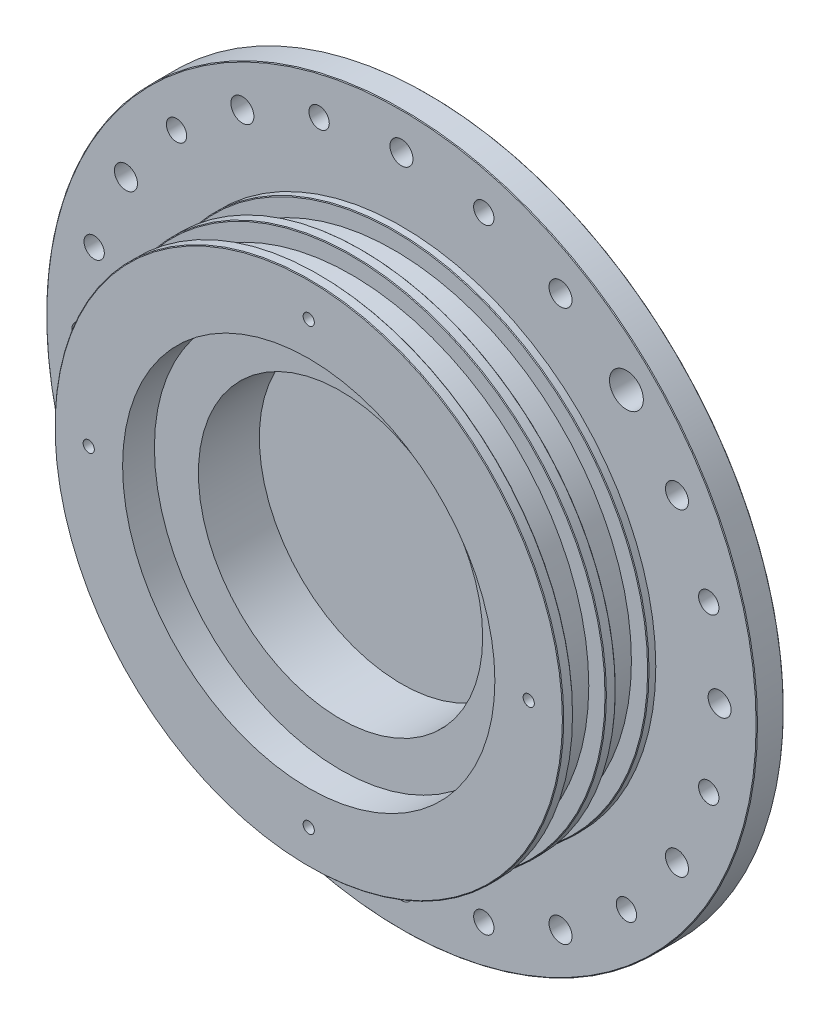
SolidWorks part; units mm, degrees
other "Marquage1"
sketch "Esquisse22" plane through (-100, 100, -114.225) normal (-0.6969, 0.6451, 0.3132) x (0.5706, 0.7634, -0.3027)
sketch "Esquisse26" plane through (-110, 110, -114.225) normal (-0.6969, 0.6451, 0.3132) x (0.5706, 0.7634, -0.3027)
sketch "Esquisse28" plane through (-110, 110, -114.225) normal (-0.6969, 0.6451, 0.3132) x (0.5706, 0.7634, -0.3027)
sketch "Esquisse31" plane through (-110, 110, -114.225) normal (-0.6969, 0.6451, 0.3132) x (0.5706, 0.7634, -0.3027)
sketch "Esquisse32" plane through (-100, 100, -114.225) normal (-0.6969, 0.6451, 0.3132) x (0.5706, 0.7634, -0.3027)
material "AISI 316 Barre d'acier inoxydable recuit (SS)"
ref_plane "Plan de face" through (0, 0, 0) normal (0, 0, 1) x (1, 0, 0)
ref_plane "Plan de dessus" through (0, 0, 0) normal (0, 1, 0) x (1, 0, 0)
ref_plane "Plan de droite" through (0, 0, 0) normal (1, 0, 0) x (0, 0, -1)
sketch "Esquisse1" plane through (0, 0, 0) normal (0, 1, 0) x (1, 0, 0)
  line L0 (87.5, 35.4) -> (0, 35.4)
  line L1 (0, 35.4) -> (0, 0)
  line L2 (0, 0) -> (75.15, 0)
  line L3 (75.15, 0) -> (75.15, 3)
  line L4 (75.15, 3) -> (70.15, 3)
  line L5 (70.15, 3) -> (70.15, 12.6)
  line L6 (70.15, 12.6) -> (75.15, 12.6)
  line L7 (75.15, 12.6) -> (75.15, 15.6)
  line L8 (75.15, 15.6) -> (70.15, 15.6)
  line L9 (70.15, 15.6) -> (70.15, 25.2)
  line L10 (70.15, 25.2) -> (75.15, 25.2)
  line L11 (75.15, 25.2) -> (75.15, 27.4)
  line L12 (75.15, 27.4) -> (87.5, 27.4)
  line L13 (87.5, 27.4) -> (87.5, 35.4)
  line L14 (0, 35.4) -> (0, 0) construction
  dimension "D1" = 8
  dimension "D2" = 2.2
  dimension "D3" = 9.6
  dimension "D4" = 3
  dimension "D5" = 9.6
  dimension "D6" = 3
  dimension "D7" = 5
  dimension "D8" = 75.15
  dimension "D9" = 87.5
revolve "Révolution1" add sketch "Esquisse1" angle 360 about L14 reverse direction yes
hole_wizard "Diamètre du perçage Ø9.0 (9)1" positions "Esquisse3" profile "Esquisse2" hole size "Ø9.0" standard "Ansi Metric"
sketch "Esquisse3" plane through (0, 0, -27.4) normal (0, 0, 1) x (1, 0, 0)
  point P0 (-87.5, 0)
  point P1 (0, 87.5)
  point P2 (0, -87.5)
  point P3 (87.5, 0)
sketch "Esquisse2" plane through (-87.5, 0, -27.4) normal (1, 0, 0) x (0, -1, 0)
  line L0 (0, 0) -> (0, 3)
  line L1 (0, 3) -> (4.5, 3)
  line L2 (4.5, 3) -> (4.5, 0)
  line L5 (4.5, 0) -> (0, 0)
  line L10 (0, 3) -> (-4.5, 3) construction
  line L11 (0, -6.35) -> (0, 107.95) construction
  dimension "Diamètre du perçage" = 9
  dimension "Profondeur du perçage" = 3
  dimension "Angle de pointe" = 180
hole_wizard "Trou taraudé M4x0.71" positions "Esquisse44" profile "Esquisse45" tap size "M4x0.7" standard "Ansi Metric"
sketch "Esquisse44" plane through (0, 0, 0) normal (0, 0, 1) x (1, 0, 0)
  point P0 (0, 65)
  dimension "D1" = 65
sketch "Esquisse45" plane through (0, 65, 0) normal (1, 0, 0) x (0, -1, 0)
  line L0 (0, 0) -> (0, 15)
  line L1 (0, 15) -> (1.65, 15)
  line L2 (1.65, 15) -> (1.65, 0)
  line L5 (1.65, 0) -> (0, 0)
  line L10 (0, 15) -> (-1.65, 15) construction
  line L11 (0, -6.35) -> (0, 107.95) construction
  dimension "Diamètre du trou pour taraudage" = 3.3
  dimension "Profondeur du trou pour taraudage" = 15
  dimension "Angle de pointe" = 180
cosmetic thread "Filetage de perçage3" parameters "D1"=15, "D2"=4
pattern_circular "Répétition circulaire3" count 4 over 360 about axis through (0, 0, -35.4) along (0, 0, 1) of "Trou taraudé M4x0.71"
hole_wizard "Dégagement M1001" positions "Esquisse7" profile "Esquisse6" hole size "M100" standard "Ansi Metric"
sketch "Esquisse7" plane through (0, 0, 0) normal (0, 0, 1) x (1, 0, 0)
  point P0 (0, 0)
sketch "Esquisse6" plane through (0, 0, 0) normal (1, 0, 0) x (0, -1, 0)
  line L0 (0, 0) -> (0, 27.4)
  line L1 (0, 27.4) -> (55, 27.4)
  line L2 (55, 27.4) -> (55, 0)
  line L5 (55, 0) -> (0, 0)
  line L10 (0, 27.4) -> (-55, 27.4) construction
  line L11 (0, -6.35) -> (0, 107.95) construction
  dimension "Diamètre du perçage" = 110
  dimension "Profondeur du perçage" = 27.4
  dimension "Angle de pointe" = 180
sketch "Esquisse8" plane through (0, 0, -35.4) normal (0, 0, -1) x (-1, 0, 0)
  line L0 (0, 0) -> (0, -108.9201) construction
  circle A0 centre (0, 0) radius 108.9201 construction
  circle A1 centre (0, 0) radius 105
  circle A2 centre (0, 0) radius 77.5
  circle A3 centre (0, 0) radius 87.5 construction
  dimension "D2" = 10
  dimension "D1" = 210
extrude "Boss.-Extru.1" add sketch "Esquisse8" against normal blind 8
ref_plane "Plan1" through (0, -105, 0) normal (0, -1, 0) x (-1, 0, 0)
sketch "Esquisse35" plane through (0, 0, -27.4) normal (0, 0, 1) x (1, 0, 0)
  circle A0 centre (0, 0) radius 55
  circle A1 centre (0, 0) radius 42
  circle A4 centre (0, 0) radius 55 construction
  dimension "D1" = 84
extrude "Boss.-Extru.4" add sketch "Esquisse35" along normal blind 18
hole_wizard "Trou taraudé M8x1.251" positions "Esquisse42" profile "Esquisse43" tap size "M8x1.25" standard "Ansi Metric"
sketch "Esquisse42" plane through (0, 0, -35.4) normal (0, 0, -1) x (-1, 0, 0)
  line L0 (0, 0) -> (0, -105) construction
  line L1 (-4.18, -105) -> (4.18, -105) construction
  point P0 (0, -94)
  point P2 (0, -50)
  point P11 (0, -94)
  dimension "D1" = 50
  dimension "D2" = 94
sketch "Esquisse43" plane through (0, -94, -35.4) normal (1, 0, 0) x (0, 1, 0)
  line L0 (0, 0) -> (0, 20)
  line L1 (0, 20) -> (3.4, 20)
  line L2 (3.4, 20) -> (3.4, 0)
  line L5 (3.4, 0) -> (0, 0)
  line L10 (0, 20) -> (-3.4, 20) construction
  line L11 (0, -6.35) -> (0, 107.95) construction
  dimension "Diamètre du trou pour taraudage" = 6.8
  dimension "Profondeur du trou pour taraudage" = 20
  dimension "Angle de pointe" = 180
cosmetic thread "Filetage de perçage1" parameters "D1"=16, "D2"=8
cosmetic thread "Filetage de perçage2" parameters "D1"=16, "D2"=8
pattern_circular "Répétition circulaire2" count 12 over 360 about axis through (0, 0, -35.4) along (0, 0, -1) of "Trou taraudé M8x1.251"
sketch "Esquisse24" plane through (0, 0, -35.4) normal (0, 0, -1) x (-1, 0, 0)
  line L0 (28.0621, 104.7291) -> (0, 0) construction
  line L1 (-54.2118, 93.8976) -> (0, 0) construction
  line L2 (0, 0) -> (0, 94) construction
  line L3 (0, 0) -> (-66.468, 66.468) construction
  circle A0 centre (-47, 81.4064) radius 5 construction
  circle A1 centre (24.329, 90.797) radius 3
  circle A2 centre (66.468, 66.468) radius 3
  circle A3 centre (90.797, 24.329) radius 3
  circle A4 centre (90.797, -24.329) radius 3
  circle A5 centre (-14, 24.2487) radius 5.1
  circle A6 centre (7.2469, 27.0459) radius 5.1
  circle A7 centre (24.2487, 14) radius 5.1
  circle A8 centre (27.0459, -7.2469) radius 5.1
  circle A9 centre (14, -24.2487) radius 5.1
  circle A10 centre (-7.2469, -27.0459) radius 5.1
  circle A11 centre (-24.2487, -14) radius 5.1
  circle A12 centre (-27.0459, 7.2469) radius 5.1
  circle A13 centre (-66.468, 66.468) radius 5
  circle A14 centre (66.468, -66.468) radius 3
  circle A15 centre (24.329, -90.797) radius 3
  circle A16 centre (-24.329, -90.797) radius 3
  circle A17 centre (-66.468, -66.468) radius 3
  circle A18 centre (-90.797, -24.329) radius 3
  circle A19 centre (-90.797, 24.329) radius 3
  circle A20 centre (-66.468, 66.468) radius 3 construction
  circle A21 centre (-24.329, 90.797) radius 3
  circle A22 centre (0, 0) radius 82.55 construction
  circle A23 centre (-66.468, 66.468) radius 8 construction
  circle A24 centre (0, 0) radius 5.1
  point P19 (0, 0)
  point P36 (0, 0)
  point P55 (0, 0)
  point P56 (0, 94)
  point P58 (0, 0)
  dimension "D1" = 6
  dimension "D3" = 10
  dimension "D6" = 10.2
  dimension "D11" = 15
  dimension "D12" = 10
  dimension "D14" = 165.1
  dimension "D15" = 16
  dimension "D2" = 94
  dimension "D4" = 94
  dimension "D7" = 28
  dimension "D9" = 45
  dimension "D10" = 15
  dimension "D13" = 94
  dimension "D5" = 12
  dimension "D8" = 8
extrude "Enlèv. mat.-Extru.15" cut sketch "Esquisse24" against normal through all and the other way through all
chamfer "Chanfrein1" distance 0.2 angle 45 7 edges at (75.15, 0, -25.2) (75.15, 0, -3) (75.15, 0, -12.6) (75.15, 0, -15.6) (-105, 0, -35.4) (-105, 0, -27.4) (75.15, 0, 0)
sketch "Esquisse25" plane through (0, 0, -35.4) normal (0, 0, -1) x (-1, 0, 0)
  line L4 (0, 0) -> (-27.0459, 7.2469) construction
  line L5 (0, 0) -> (-50, 0) construction
  line L8 (-10.1, 3.1378) -> (-10.1, -3.1378)
  line L13 (10.1, 3.1378) -> (10.1, -3.1378)
  arc A1 (-10.1, 4.6043) -> (10.1, 4.6043) centre (0, 0) cw construction
  arc A2 (10.1, -4.6043) -> (-10.1, -4.6043) centre (0, 0) cw construction
  arc A3 (10.1, 3.1378) -> (9.4049, 5.8956) centre (7.191, 3.8711) ccw
  arc A4 (-10.1, 3.1378) -> (-9.4049, 5.8956) centre (-7.191, 3.8711) cw
  arc A5 (10.1, -3.1378) -> (9.4049, -5.8956) centre (7.191, -3.8711) cw
  arc A6 (-10.1, -3.1378) -> (-9.4049, -5.8956) centre (-7.191, -3.8711) ccw
  arc A7 (-9.4049, 5.8956) -> (9.4049, 5.8956) centre (0, 0) cw
  arc A8 (-9.4049, -5.8956) -> (9.4049, -5.8956) centre (0, 0) ccw
  point P5 (0, 0)
  point P14 (0, 0)
  point P15 (-50, 0)
  point P16 (0, 0)
  point P19 (10.1, 4.6043)
  line B0 (-24.9287, -1.7061) -> (-33.3561, 0.552) construction
  line B1 (-33.3561, 0.552) -> (-29.1632, 16.2) construction
  line B2 (-29.1632, 16.2) -> (-20.7358, 13.9419) construction
  line B3 (-20.7358, 13.9419) -> (-24.9287, -1.7061) construction
  line B4 (-22.8322, 6.1179) -> (-31.2596, 8.376) construction
  line B5 (-27.0459, 7.2469) -> (-29.1424, -0.5771) construction
  line B6 (-22.5347, 14.4239) -> (-27.3643, 15.718)
  line B7 (-26.7275, -1.2241) -> (-31.5572, 0.07)
  arc B8 (-33.3561, 0.552) -> (-29.1632, 16.2) centre (-27.0459, 7.2469) cw construction
  arc B9 (-24.9287, -1.7061) -> (-20.7358, 13.9419) centre (-27.0459, 7.2469) ccw construction
  arc B10 (-22.8033, -0.9164) -> (-19.29, 12.1953) centre (-27.0459, 7.2469) ccw
  arc B11 (-19.29, 12.1953) -> (-19.4952, 12.5745) centre (-16.7609, 13.8089) cw
  arc B12 (-19.4952, 12.5745) -> (-21.9939, 14.3309) centre (-22.2295, 11.3402) ccw
  arc B13 (-21.9939, 14.3309) -> (-22.5347, 14.4239) centre (-21.7582, 17.3217) cw
  arc B14 (-27.8791, 15.9079) -> (-27.3643, 15.718) centre (-26.5878, 18.6158) ccw
  arc B15 (-30.9212, 15.6361) -> (-27.8791, 15.9079) centre (-29.1704, 13.2) cw
  arc B16 (-31.2885, 15.4103) -> (-30.9212, 15.6361) centre (-32.672, 18.0722) ccw
  arc B17 (-34.8018, 2.2986) -> (-31.2885, 15.4103) centre (-27.0459, 7.2469) cw
  arc B18 (-34.8018, 2.2986) -> (-34.5966, 1.9193) centre (-37.3309, 0.685) cw
  arc B19 (-34.5966, 1.9193) -> (-32.098, 0.1629) centre (-31.8623, 3.1537) ccw
  arc B20 (-32.098, 0.1629) -> (-31.5572, 0.07) centre (-32.3336, -2.8278) cw
  arc B21 (-26.2127, -1.414) -> (-26.7275, -1.2241) centre (-27.504, -4.1219) ccw
  arc B22 (-23.1707, -1.1423) -> (-26.2127, -1.414) centre (-24.9215, 1.2939) cw
  arc B23 (-22.8033, -0.9164) -> (-23.1707, -1.1423) centre (-21.4198, -3.5784) ccw
  line B24 (-5.7352, 26.1336) -> (-8.2352, 30.4638)
  line B25 (-19.7648, 18.0336) -> (-22.2648, 22.3638)
  arc B26 (-16.7724, 15.4764) -> (-5.0167, 22.2635) centre (-14, 24.2487) ccw
  arc B27 (-5.0167, 22.2635) -> (-4.8937, 22.6768) centre (-2.0874, 21.6161) cw
  arc B28 (-4.8937, 22.6768) -> (-5.4185, 25.6855) centre (-7.6999, 23.7374) ccw
  arc B29 (-5.4185, 25.6855) -> (-5.7352, 26.1336) centre (-3.1371, 27.6336) cw
  arc B30 (-8.4649, 30.9621) -> (-8.2352, 30.4638) centre (-5.6371, 31.9638) ccw
  arc B31 (-10.8082, 32.921) -> (-8.4649, 30.9621) centre (-11.2928, 29.9604) cw
  arc B32 (-11.2276, 33.0211) -> (-10.8082, 32.921) centre (-10.3236, 35.8816) ccw
  arc B33 (-22.9833, 26.2339) -> (-11.2276, 33.0211) centre (-14, 24.2487) cw
  arc B34 (-22.9833, 26.2339) -> (-23.1063, 25.8207) centre (-25.9126, 26.8813) cw
  arc B35 (-23.1063, 25.8207) -> (-22.5815, 22.8119) centre (-20.3001, 24.76) ccw
  arc B36 (-22.5815, 22.8119) -> (-22.2648, 22.3638) centre (-24.8629, 20.8638) cw
  arc B37 (-19.5351, 17.5353) -> (-19.7648, 18.0336) centre (-22.3629, 16.5336) ccw
  arc B38 (-17.1918, 15.5764) -> (-19.5351, 17.5353) centre (-16.7072, 18.537) cw
  arc B39 (-16.7724, 15.4764) -> (-17.1918, 15.5764) centre (-17.6764, 12.6158) ccw
  line B40 (14.4239, 22.5347) -> (15.718, 27.3643)
  line B41 (-1.2241, 26.7275) -> (0.07, 31.5572)
  arc B42 (-0.9164, 22.8033) -> (12.1953, 19.29) centre (7.2469, 27.0459) ccw
  arc B43 (12.1953, 19.29) -> (12.5745, 19.4952) centre (13.8089, 16.7609) cw
  arc B44 (12.5745, 19.4952) -> (14.3309, 21.9939) centre (11.3402, 22.2295) ccw
  arc B45 (14.3309, 21.9939) -> (14.4239, 22.5347) centre (17.3217, 21.7582) cw
  arc B46 (15.9079, 27.8791) -> (15.718, 27.3643) centre (18.6158, 26.5878) ccw
  arc B47 (15.6361, 30.9212) -> (15.9079, 27.8791) centre (13.2, 29.1704) cw
  arc B48 (15.4103, 31.2885) -> (15.6361, 30.9212) centre (18.0722, 32.672) ccw
  arc B49 (2.2986, 34.8018) -> (15.4103, 31.2885) centre (7.2469, 27.0459) cw
  arc B50 (2.2986, 34.8018) -> (1.9193, 34.5966) centre (0.685, 37.3309) cw
  arc B51 (1.9193, 34.5966) -> (0.1629, 32.098) centre (3.1537, 31.8623) ccw
  arc B52 (0.1629, 32.098) -> (0.07, 31.5572) centre (-2.8278, 32.3336) cw
  arc B53 (-1.414, 26.2127) -> (-1.2241, 26.7275) centre (-4.1219, 27.504) ccw
  arc B54 (-1.1423, 23.1707) -> (-1.414, 26.2127) centre (1.2939, 24.9215) cw
  arc B55 (-0.9164, 22.8033) -> (-1.1423, 23.1707) centre (-3.5784, 21.4198) ccw
  line B56 (26.1336, 5.7352) -> (30.4638, 8.2352)
  line B57 (18.0336, 19.7648) -> (22.3638, 22.2648)
  arc B58 (15.4764, 16.7724) -> (22.2635, 5.0167) centre (24.2487, 14) ccw
  arc B59 (22.2635, 5.0167) -> (22.6768, 4.8937) centre (21.6161, 2.0874) cw
  arc B60 (22.6768, 4.8937) -> (25.6855, 5.4185) centre (23.7374, 7.6999) ccw
  arc B61 (25.6855, 5.4185) -> (26.1336, 5.7352) centre (27.6336, 3.1371) cw
  arc B62 (30.9621, 8.4649) -> (30.4638, 8.2352) centre (31.9638, 5.6371) ccw
  arc B63 (32.921, 10.8082) -> (30.9621, 8.4649) centre (29.9604, 11.2928) cw
  arc B64 (33.0211, 11.2276) -> (32.921, 10.8082) centre (35.8816, 10.3236) ccw
  arc B65 (26.2339, 22.9833) -> (33.0211, 11.2276) centre (24.2487, 14) cw
  arc B66 (26.2339, 22.9833) -> (25.8207, 23.1063) centre (26.8813, 25.9126) cw
  arc B67 (25.8207, 23.1063) -> (22.8119, 22.5815) centre (24.76, 20.3001) ccw
  arc B68 (22.8119, 22.5815) -> (22.3638, 22.2648) centre (20.8638, 24.8629) cw
  arc B69 (17.5353, 19.5351) -> (18.0336, 19.7648) centre (16.5336, 22.3629) ccw
  arc B70 (15.5764, 17.1918) -> (17.5353, 19.5351) centre (18.537, 16.7072) cw
  arc B71 (15.4764, 16.7724) -> (15.5764, 17.1918) centre (12.6158, 17.6764) ccw
  line B72 (22.5347, -14.4239) -> (27.3643, -15.718)
  line B73 (26.7275, 1.2241) -> (31.5572, -0.07)
  arc B74 (22.8033, 0.9164) -> (19.29, -12.1953) centre (27.0459, -7.2469) ccw
  arc B75 (19.29, -12.1953) -> (19.4952, -12.5745) centre (16.7609, -13.8089) cw
  arc B76 (19.4952, -12.5745) -> (21.9939, -14.3309) centre (22.2295, -11.3402) ccw
  arc B77 (21.9939, -14.3309) -> (22.5347, -14.4239) centre (21.7582, -17.3217) cw
  arc B78 (27.8791, -15.9079) -> (27.3643, -15.718) centre (26.5878, -18.6158) ccw
  arc B79 (30.9212, -15.6361) -> (27.8791, -15.9079) centre (29.1704, -13.2) cw
  arc B80 (31.2885, -15.4103) -> (30.9212, -15.6361) centre (32.672, -18.0722) ccw
  arc B81 (34.8018, -2.2986) -> (31.2885, -15.4103) centre (27.0459, -7.2469) cw
  arc B82 (34.8018, -2.2986) -> (34.5966, -1.9193) centre (37.3309, -0.685) cw
  arc B83 (34.5966, -1.9193) -> (32.098, -0.1629) centre (31.8623, -3.1537) ccw
  arc B84 (32.098, -0.1629) -> (31.5572, -0.07) centre (32.3336, 2.8278) cw
  arc B85 (26.2127, 1.414) -> (26.7275, 1.2241) centre (27.504, 4.1219) ccw
  arc B86 (23.1707, 1.1423) -> (26.2127, 1.414) centre (24.9215, -1.2939) cw
  arc B87 (22.8033, 0.9164) -> (23.1707, 1.1423) centre (21.4198, 3.5784) ccw
  line B88 (5.7352, -26.1336) -> (8.2352, -30.4638)
  line B89 (19.7648, -18.0336) -> (22.2648, -22.3638)
  arc B90 (16.7724, -15.4764) -> (5.0167, -22.2635) centre (14, -24.2487) ccw
  arc B91 (5.0167, -22.2635) -> (4.8937, -22.6768) centre (2.0874, -21.6161) cw
  arc B92 (4.8937, -22.6768) -> (5.4185, -25.6855) centre (7.6999, -23.7374) ccw
  arc B93 (5.4185, -25.6855) -> (5.7352, -26.1336) centre (3.1371, -27.6336) cw
  arc B94 (8.4649, -30.9621) -> (8.2352, -30.4638) centre (5.6371, -31.9638) ccw
  arc B95 (10.8082, -32.921) -> (8.4649, -30.9621) centre (11.2928, -29.9604) cw
  arc B96 (11.2276, -33.0211) -> (10.8082, -32.921) centre (10.3236, -35.8816) ccw
  arc B97 (22.9833, -26.2339) -> (11.2276, -33.0211) centre (14, -24.2487) cw
  arc B98 (22.9833, -26.2339) -> (23.1063, -25.8207) centre (25.9126, -26.8813) cw
  arc B99 (23.1063, -25.8207) -> (22.5815, -22.8119) centre (20.3001, -24.76) ccw
  arc B100 (22.5815, -22.8119) -> (22.2648, -22.3638) centre (24.8629, -20.8638) cw
  arc B101 (19.5351, -17.5353) -> (19.7648, -18.0336) centre (22.3629, -16.5336) ccw
  arc B102 (17.1918, -15.5764) -> (19.5351, -17.5353) centre (16.7072, -18.537) cw
  arc B103 (16.7724, -15.4764) -> (17.1918, -15.5764) centre (17.6764, -12.6158) ccw
  line B104 (-14.4239, -22.5347) -> (-15.718, -27.3643)
  line B105 (1.2241, -26.7275) -> (-0.07, -31.5572)
  arc B106 (0.9164, -22.8033) -> (-12.1953, -19.29) centre (-7.2469, -27.0459) ccw
  arc B107 (-12.1953, -19.29) -> (-12.5745, -19.4952) centre (-13.8089, -16.7609) cw
  arc B108 (-12.5745, -19.4952) -> (-14.3309, -21.9939) centre (-11.3402, -22.2295) ccw
  arc B109 (-14.3309, -21.9939) -> (-14.4239, -22.5347) centre (-17.3217, -21.7582) cw
  arc B110 (-15.9079, -27.8791) -> (-15.718, -27.3643) centre (-18.6158, -26.5878) ccw
  arc B111 (-15.6361, -30.9212) -> (-15.9079, -27.8791) centre (-13.2, -29.1704) cw
  arc B112 (-15.4103, -31.2885) -> (-15.6361, -30.9212) centre (-18.0722, -32.672) ccw
  arc B113 (-2.2986, -34.8018) -> (-15.4103, -31.2885) centre (-7.2469, -27.0459) cw
  arc B114 (-2.2986, -34.8018) -> (-1.9193, -34.5966) centre (-0.685, -37.3309) cw
  arc B115 (-1.9193, -34.5966) -> (-0.1629, -32.098) centre (-3.1537, -31.8623) ccw
  arc B116 (-0.1629, -32.098) -> (-0.07, -31.5572) centre (2.8278, -32.3336) cw
  arc B117 (1.414, -26.2127) -> (1.2241, -26.7275) centre (4.1219, -27.504) ccw
  arc B118 (1.1423, -23.1707) -> (1.414, -26.2127) centre (-1.2939, -24.9215) cw
  arc B119 (0.9164, -22.8033) -> (1.1423, -23.1707) centre (3.5784, -21.4198) ccw
  line B120 (-26.1336, -5.7352) -> (-30.4638, -8.2352)
  line B121 (-18.0336, -19.7648) -> (-22.3638, -22.2648)
  arc B122 (-15.4764, -16.7724) -> (-22.2635, -5.0167) centre (-24.2487, -14) ccw
  arc B123 (-22.2635, -5.0167) -> (-22.6768, -4.8937) centre (-21.6161, -2.0874) cw
  arc B124 (-22.6768, -4.8937) -> (-25.6855, -5.4185) centre (-23.7374, -7.6999) ccw
  arc B125 (-25.6855, -5.4185) -> (-26.1336, -5.7352) centre (-27.6336, -3.1371) cw
  arc B126 (-30.9621, -8.4649) -> (-30.4638, -8.2352) centre (-31.9638, -5.6371) ccw
  arc B127 (-32.921, -10.8082) -> (-30.9621, -8.4649) centre (-29.9604, -11.2928) cw
  arc B128 (-33.0211, -11.2276) -> (-32.921, -10.8082) centre (-35.8816, -10.3236) ccw
  arc B129 (-26.2339, -22.9833) -> (-33.0211, -11.2276) centre (-24.2487, -14) cw
  arc B130 (-26.2339, -22.9833) -> (-25.8207, -23.1063) centre (-26.8813, -25.9126) cw
  arc B131 (-25.8207, -23.1063) -> (-22.8119, -22.5815) centre (-24.76, -20.3001) ccw
  arc B132 (-22.8119, -22.5815) -> (-22.3638, -22.2648) centre (-20.8638, -24.8629) cw
  arc B133 (-17.5353, -19.5351) -> (-18.0336, -19.7648) centre (-16.5336, -22.3629) ccw
  arc B134 (-15.5764, -17.1918) -> (-17.5353, -19.5351) centre (-18.537, -16.7072) cw
  arc B135 (-15.4764, -16.7724) -> (-15.5764, -17.1918) centre (-12.6158, -17.6764) ccw
  line B136 (0, 0) -> (0, 11.1) construction
  line B137 (10.1, 4.6043) -> (10.1, -4.6043) construction
  line B138 (-10.1, 4.6043) -> (-10.1, -4.6043) construction
  circle B139 centre (0, 0) radius 11.1 construction
  dimension "D1" = 28
  dimension "D3" = 8
  dimension "D4" = 3
  dimension "D5" = 14.382
  dimension "D2" = 15
sketch_block_instance "Bloc1-1"
sketch_block "Bloc1" parameters "D2"=9.2, "D3"=3, "D1"=16.2, "D4"=2.5, "D5"=0.7323
sketch_block_instance "Bloc1-2"
sketch_block_instance "Bloc1-3"
sketch_block_instance "Bloc1-4"
sketch_block_instance "Bloc1-5"
sketch_block_instance "Bloc1-6"
sketch_block_instance "Bloc1-7"
sketch_block_instance "Bloc1-8"
sketch_block_instance "Bloc2-1"
sketch_block "Bloc2" parameters "D1"=20.2
sketch_block_instance "Bloc2-2"
extrude "Enlèv. mat.-Extru.18" cut sketch "Esquisse25" against normal blind 2
sketch "Esquisse36" plane through (0, 0, -27.4) normal (0, 0, 1) x (1, 0, 0)
  circle A0 centre (-27.0459, -7.2469) radius 5.1
  circle A1 centre (-27.0459, -7.2469) radius 5.1 construction
  circle A2 centre (-24.2487, 14) radius 5.1
  circle A3 centre (-7.2469, 27.0459) radius 5.1
  circle A4 centre (14, 24.2487) radius 5.1
  circle A5 centre (27.0459, 7.2469) radius 5.1
  circle A6 centre (24.2487, -14) radius 5.1
  circle A7 centre (7.2469, -27.0459) radius 5.1
  circle A8 centre (-14, -24.2487) radius 5.1
  circle A9 centre (0, 0) radius 5.1
  circle A11 centre (0, 0) radius 5.1 construction
  point P14 (0, 0)
  dimension "D1" = 8
extrude "Boss.-Extru.5" add sketch "Esquisse36" against normal blind 5
sketch "Esquisse37" plane through (0, 0, -35.4) normal (0, 0, -1) x (-1, 0, 0)
  point P0 (-14, 24.2487)
  point P1 (14, -24.2487)
ref_plane "Plan2" through (0, 0, 0) normal (-0.866, 0.5, 0) x (0, 0, 1)
sketch "Esquisse38" plane through (0, 0, 0) normal (-0.866, 0.5, 0) x (0, 0, 1)
  line L0 (-35.4, 28) -> (-30.4, 28)
  line L1 (-30.4, 28) -> (-32.4, 33.1)
  line L2 (-32.4, 33.1) -> (-35.4, 33.1)
  line L4 (-35.4, 33.1) -> (-35.4, 28)
  dimension "D1" = 5.1
  dimension "D2" = 5
  dimension "D3" = 3
revolve "Enlèvement de matière-Révolution4" cut sketch "Esquisse38" angle 360 about L0
pattern_circular "Répétition circulaire1" count 8 over 360 about axis through (0, 0, -32.4) along (0, 0, -1) of "Enlèvement de matière-Révolution4"
sketch "Esquisse39" plane through (0, 0, 0) normal (-0.866, 0.5, 0) x (0, 0, 1)
  line L0 (0, 0) -> (-35.4, 0) construction
  line L1 (-35.4, 104.8) -> (-35.4, -104.8) construction
  line L2 (-35.4, 0) -> (-35.4, 7.1)
  line L3 (-35.4, 7.1) -> (-32.4, 7.1)
  line L4 (-32.4, 7.1) -> (-30.4, 0)
  line L5 (-30.4, 0) -> (-35.4, 0)
  dimension "D1" = 5
  dimension "D2" = 3
  dimension "D3" = 7.1
revolve "Enlèvement de matière-Révolution5" cut sketch "Esquisse39" angle 360 about L0
equation "\"_à\"=76.5769"
